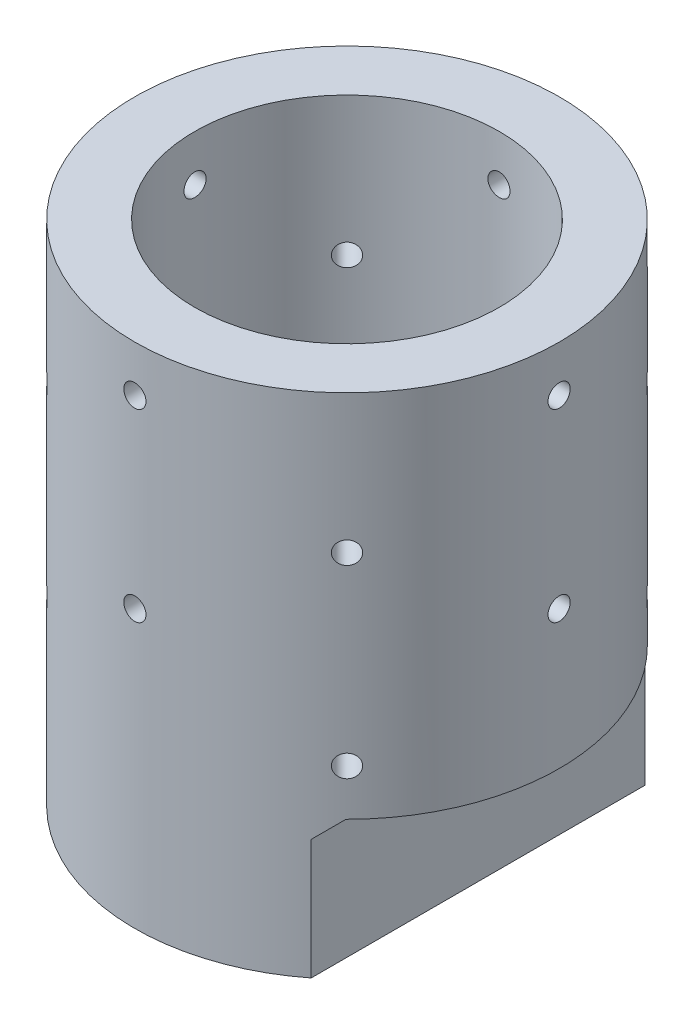
SolidWorks part; units mm, degrees
ref_plane "Спереди" through (0, 0, 0) normal (0, 0, 1) x (1, 0, 0)
ref_plane "Сверху" through (0, 0, 0) normal (0, 1, 0) x (1, 0, 0)
ref_plane "Справа" through (0, 0, 0) normal (1, 0, 0) x (0, 0, -1)
sketch "Эскиз1" plane through (0, 0, 0) normal (0, 1, 0) x (1, 0, 0)
  circle A0 centre (0, 0) radius 23
  dimension "D1" = 46
extrude "Бобышка-Вытянуть1" add sketch "Эскиз1" along normal blind 5
sketch "Эскиз2" plane through (0, 5, 0) normal (0, 1, 0) x (1, 0, 0)
  circle A0 centre (0, 0) radius 23
  circle A1 centre (0, 0) radius 16.5
  circle A2 centre (0, 0) radius 23 construction
  dimension "D1" = 33
  dimension "D2" = 0
extrude "Бобышка-Вытянуть2" add sketch "Эскиз2" along normal blind 35
chamfer "Фаска8" distance 2 angle 45 1 edges at (0, 5, 16.5)
sketch "Эскиз3" plane through (0, 0, 0) normal (1, 0, 0) x (0, 0, -1)
  line L0 (-23, 20) -> (28.0263, 20) construction
  line L1 (-23, 40) -> (-23, 0) construction
  line L2 (16.5, 40) -> (-16.5, 40) construction
  circle A1 centre (0, 35) radius 1.2
  dimension "D1" = 2.4
  dimension "D2" = 5
extrude "Вырез-Вытянуть1" cut sketch "Эскиз3" against normal through all
ref_plane "Плоскость1" through (0, 0, 0) normal (0.7071, 0, 0.7071) x (0, -1, 0)
sketch "Эскиз4" plane through (0, 0, 0) normal (0.7071, 0, 0.7071) x (0, -1, 0)
  line L0 (-20, 23) -> (-20, -30.0625) construction
  line L1 (0, 23) -> (-40, 23) construction
  line L3 (0, -23) -> (0, 23) construction
  circle A1 centre (-5, 0) radius 1.2
  dimension "D1" = 5
  dimension "D2" = 2.4
extrude "Вырез-Вытянуть2" cut sketch "Эскиз4" against normal through all from offset 16.3 offset against normal yes
pattern_circular "Круговой массив1" count 4 over 360 about axis through (0, 5, 0) along (0, -1, 0) of "Вырез-Вытянуть2"
pattern_circular "Круговой массив2" count 4 over 360 about axis through (0, 5, 0) along (0, -1, 0) of "Вырез-Вытянуть1"
pattern_linear "Линейный массив3" count 2 spacing 20 along (0, 1, 0) of "Круговой массив1"
pattern_linear "Линейный массив4" count 2 spacing 20 along (0, -1, 0) of "Круговой массив2"
sketch "Эскиз12" plane through (0, 0, 0) normal (0, -1, 0) x (1, 0, 0)
  line L1 (14.207, 18.0876) -> (14.207, -18.0876)
  line L20 (0, 15) -> (-2.7835, 17.7835)
  line L21 (-2.7835, -17.7835) -> (0, -15)
  line L22 (0, -15) -> (0, 15)
  line L23 (0, 15) -> (-2.7835, 17.7835)
  line L24 (-2.7835, -17.7835) -> (0, -15)
  line L25 (0, -15) -> (0, 15)
  circle A6 centre (0, 0) radius 23 construction
  arc A7 (14.207, 18.0876) -> (14.207, -18.0876) centre (0, 0) ccw
  arc A13 (-2.7835, 17.7835) -> (-2.7835, -17.7835) centre (0, 0) ccw
  arc A14 (-2.7835, 17.7835) -> (-2.7835, -17.7835) centre (0, 0) ccw
  dimension "D1" = 0
extrude "Бобышка-Вытянуть3" add sketch "Эскиз12" along normal blind 15 contours L1 region at (13.6153, 0, 0)
sketch "Эскиз13" plane through (0, -15, 0) normal (0, -1, 0) x (1, 0, 0)
  line L14 (-2.6786, -18.1029) -> (0.3, -15.1243)
  line L15 (0.3, 15.1243) -> (-2.6786, 18.1029)
  line L16 (0.3, -15.1243) -> (0.3, 15.1243)
  line L17 (-2.6786, -18.1029) -> (0.3, -15.1243)
  line L18 (0.3, 15.1243) -> (-2.6786, 18.1029)
  line L19 (0.3, -15.1243) -> (0.3, 15.1243)
  arc A5 (-2.6786, 18.1029) -> (-2.6786, -18.1029) centre (0, 0) ccw
  arc A6 (-2.6786, 18.1029) -> (-2.6786, -18.1029) centre (0, 0) ccw
  dimension "D1" = 0.3
extrude "Вырез-Вытянуть10" cut sketch "Эскиз13" against normal up to surface (15 mm away) up to face at (18.6035, 0, 0)
chamfer "Фаска4" distance 2 angle 45 1 edges at (14.207, 0, 0)
chamfer "Фаска6" distance 2 angle 45 4 edges at (-1.1893, 0, -16.6136) (-18.3, 0, 0) (0.3, 0, 0) (-1.1893, 0, 16.6136)
chamfer "Фаска7" distance 2 angle 45 4 edges at (-1.1893, -15, -16.6136) (-18.3, -15, 0) (-1.1893, -15, 16.6136) (0.3, -15, 0)
